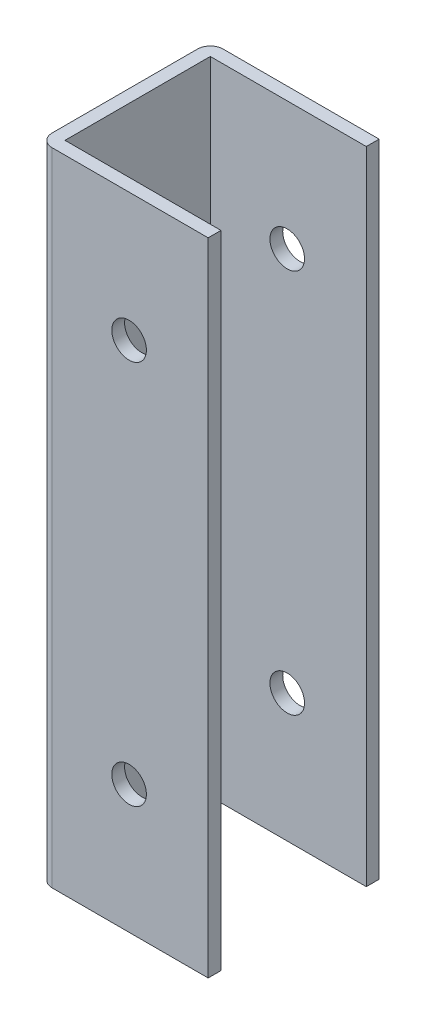
SolidWorks part; units mm, degrees
ref_plane "Спереди" through (0, 0, 0) normal (0, 0, 1) x (1, 0, 0)
ref_plane "Сверху" through (0, 0, 0) normal (0, 1, 0) x (1, 0, 0)
ref_plane "Справа" through (0, 0, 0) normal (1, 0, 0) x (0, 0, -1)
sketch "Эскиз1" plane through (0, 0, 0) normal (0, 1, 0) x (1, 0, 0)
  line L1 (-37, 20) -> (37, 20)
  line L2 (-40, 17) -> (-40, -17)
  line L3 (-37, -20) -> (37, -20)
  line L4 (40, 17) -> (40, -17)
  line L5 (-40, 20) -> (40, -20) construction
  line L6 (-40, -20) -> (40, 20) construction
  arc A0 (-37, 20) -> (-40, 17) centre (-37, 17) ccw
  arc A1 (-40, -17) -> (-37, -20) centre (-37, -17) ccw
  arc A2 (37, -20) -> (40, -17) centre (37, -17) ccw
  arc A3 (37, 20) -> (40, 17) centre (37, 17) cw
  point P0 (0, 0)
  dimension "D1" = 3
extrude "Вытянуть-Тонкостенный1" add sketch "Эскиз1" along normal blind 150 thin thin type one direction reverse wall 3
sketch "Эскиз2" plane through (0, 150, 0) normal (0, 1, 0) x (1, 0, 0)
  line L1 (-0.5, -21.5541) -> (41.1465, -21.5541)
  line L2 (-0.5, -21.5541) -> (-0.5, 20.9728)
  line L3 (-0.5, 20.9728) -> (41.1465, 20.9728)
  line L4 (41.1465, -21.5541) -> (41.1465, 20.9728)
extrude "Вырез-Вытянуть1" cut sketch "Эскиз2" against normal through all
sketch "Эскиз3" plane through (0, 0, -20) normal (0, 0, -1) x (-1, 0, 0)
  circle A0 centre (19, 120) radius 4.05
  circle A1 centre (19, 30) radius 4.05
  dimension "D1" = 2
extrude "Вырез-Вытянуть2" cut sketch "Эскиз3" against normal through all
